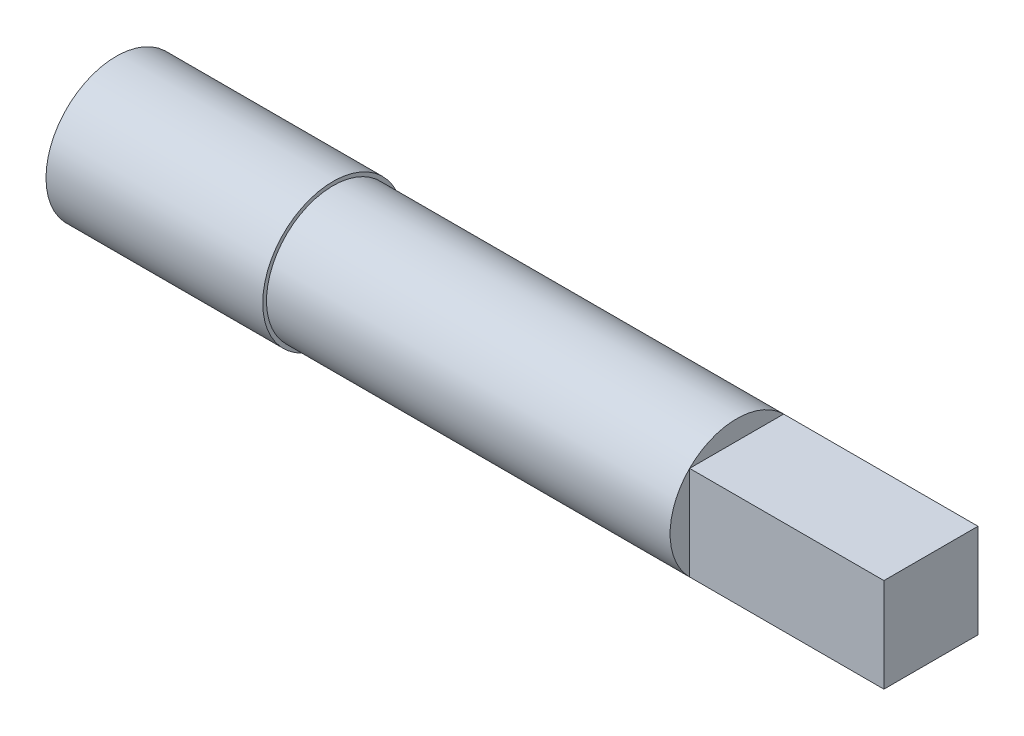
SolidWorks part; units mm, degrees
ref_plane "Alzado" through (0, 0, 0) normal (1, 0, 0) x (0, 1, 0)
ref_plane "Planta" through (0, 0, 0) normal (0, 0, 1) x (0, 1, 0)
ref_plane "Vista lateral" through (0, 0, 0) normal (0, 1, 0) x (-1, 0, 0)
sketch "Croquis1" plane through (0, 0, 0) normal (1, 0, 0) x (0, 1, 0)
  circle A0 centre (0, 0) radius 2.35
  circle A2 centre (0, 0) radius 2.225
  dimension "D1" = 4.7
  dimension "D2" = 4.45
extrude "Saliente-Extruir1" add sketch "Croquis1" along normal blind 7.25 contours A2 | A0 A2 region at (0, -2.2835, 0) region at (0, 0, 0)
extrude "Saliente-Extruir2" add sketch "Croquis1<3>" along normal blind 20 from surface contours A2 region at (0, 0, 0) starting at face at (7.25, 0, -2.35)
sketch "Croquis1<3>" plane through (0, 0, 0) normal (1, 0, 0) x (0, 1, 0) same geometry as "Croquis1"
sketch "Croquis3" plane through (27.25, 0, 0) normal (1, 0, 0) x (0, 1, 0)
  line L1 (-1.5733, -1.5733) -> (1.5733, -1.5733)
  line L2 (-1.5733, -1.5733) -> (-1.5733, 1.5733)
  line L3 (-1.5733, 1.5733) -> (1.5733, 1.5733)
  line L4 (1.5733, -1.5733) -> (1.5733, 1.5733)
  line L5 (-1.5733, -1.5733) -> (1.5733, 1.5733) construction
  line L6 (-1.5733, 1.5733) -> (1.5733, -1.5733) construction
  circle A0 centre (0, 0) radius 2.225 construction
  circle A1 centre (0, 0) radius 2.225 construction
  circle A2 centre (0, 0) radius 2.225
  point P0 (0, 0)
  circle M6 centre (0, 0) radius 2.225
extrude "Cortar-Extruir1" cut sketch "Croquis3" against normal blind 6.5 contours L3 M6 | L2 M6 | L4 M6 | L1 M6 region at (27.25, -1.8376, 0) region at (27.25, 0, -1.8376) region at (27.25, 1.8376, 0) region at (27.25, 0, 1.8376)
